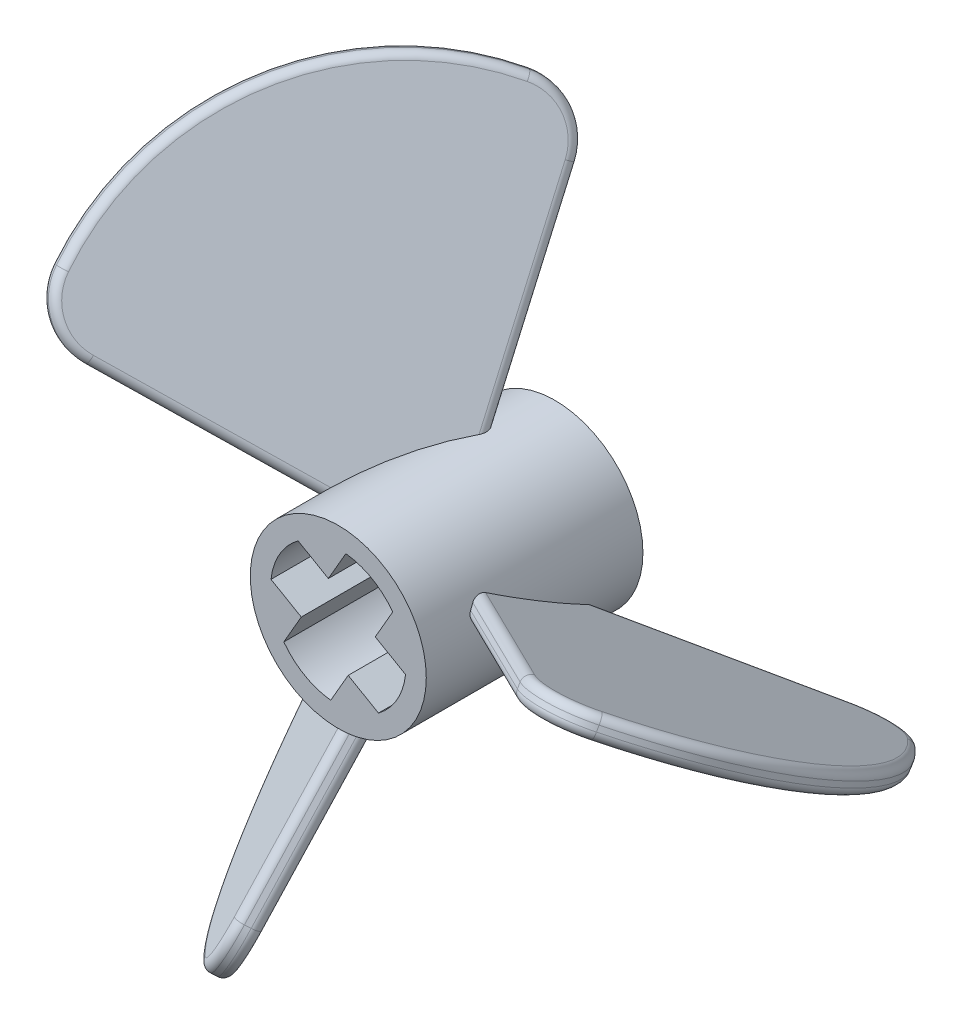
SolidWorks part; units mm, degrees
ref_plane "Front Plane" through (0, 0, 0) normal (0, 0, 1) x (1, 0, 0)
ref_plane "Top Plane" through (0, 0, 0) normal (0, 1, 0) x (1, 0, 0)
ref_plane "Right Plane" through (0, 0, 0) normal (1, 0, 0) x (0, 0, -1)
sketch "Sketch1" plane through (0, 0, 0) normal (0, 0, 1) x (1, 0, 0)
  circle A0 centre (0, 0) radius 3.25
  dimension "D1" = 6.5
extrude "Boss-Extrude1" add sketch "Sketch1" along normal mid plane 8
ref_plane "Plane1" through (12, 0, 0) normal (1, 0, 0) x (0, 0, -1)
ref_axis "Axis1" through (2.75, 0, 0) along (-1, 0, 0)
ref_plane "Plane2" through (0, 0, 0) normal (0, 0.866, -0.5) x (-1, 0, 0)
sketch "Sketch6" plane through (0, 0, 0) normal (0, 0.866, -0.5) x (-1, 0, 0)
  line L0 (0, 0) -> (-10, 8)
  line L1 (0, 0) -> (-10, -8)
  arc A0 (-10, -8) -> (-10, 8) centre (-4, 0) cw
  dimension "D4" = 10
  dimension "D1" = 16
  dimension "D2" = 10
  dimension "D3" = 8
extrude "Boss-Extrude4" add sketch "Sketch6" along normal mid plane 0.8
fillet "Fillet1" radius 2 2 edges at (10, -4, -6.9282) (10, 4, 6.9282)
pattern_circular "CirPattern2" count 3 over 360 about axis through (0, 0, 4) along (0, 0, -1) of "Boss-Extrude4", "Fillet1"
sketch "Sketch7" plane through (0, 0, 4) normal (0, 0, 1) x (1, 0, 0)
  line L0 (0.2796, 2.4843) -> (-0.366, 1.366)
  line L1 (2.0117, 1.4843) -> (1.366, 0.366)
  line L2 (-1.4843, 2.0117) -> (-0.366, 1.366)
  line L3 (-2.4843, 0.2796) -> (-1.366, -0.366)
  line L4 (1.366, 0.366) -> (2.4843, -0.2796)
  line L5 (-1.366, -0.366) -> (-2.0117, -1.4843)
  line L6 (0.366, -1.366) -> (1.4843, -2.0117)
  line L7 (0.366, -1.366) -> (-0.2796, -2.4843)
  line L8 (0, 0) -> (-6.915, 3.9924) construction
  line L9 (0, 0) -> (0, 6.4328) construction
  arc A1 (-1.4843, 2.0117) -> (-2.4843, 0.2796) centre (0, 0) ccw
  arc A2 (-2.0117, -1.4843) -> (-0.2796, -2.4843) centre (0, 0) ccw
  arc A3 (2.0117, 1.4843) -> (0.2796, 2.4843) centre (0, 0) ccw
  arc A4 (1.4843, -2.0117) -> (2.4843, -0.2796) centre (0, 0) ccw
  dimension "D1" = 5
  dimension "D2" = 1
  dimension "D3" = 2
  dimension "D4" = 1
  dimension "D5" = 2
  dimension "D6" = 60
extrude "Cut-Extrude1" cut sketch "Sketch7" against normal up to next
fillet "Fillet2" radius 0.3 30 edges at (-1.2059, -6.1142, 4.2863) (-2.1492, -10.4008, 6.5835) (-7.3, -11.9512, 0.2) (-8.5327, -6.7153, -6.1835) (-0.5875, -6.3333, 3.8035) (-1.5492, -10.7472, 6.1835) (-6.7, -12.2976, -0.2) (-7.9327, -7.0617, -6.5835) (-5.191, 3.6755, 3.8035) (-8.5327, 6.7153, 6.1835) (-7.3, 11.9512, -0.2) (-1.2059, 6.1142, -4.2863) (-0.5875, 6.3333, -3.8035) (-4.6921, 4.1014, 4.2863) (-7.9327, 7.0617, 6.5835) (-6.7, 12.2976, 0.2) (5.7786, -2.6578, -3.8035) (10.082, -4.0319, -6.1835) (14, -0.3464, 0.2) (10.082, 3.3391, 6.5835) (5.898, -2.0128, -4.2863) (10.082, -3.3391, -6.5835) (14, 0.3464, -0.2) (10.082, 4.0319, 6.1835) (-5.191, -3.6755, -3.8035) (-4.6921, -4.1014, -4.2863) (-2.1492, 10.4008, -6.5835) (-1.5492, 10.7472, -6.1835) (5.898, 2.0128, 4.2863) (5.7786, 2.6578, 3.8035)
